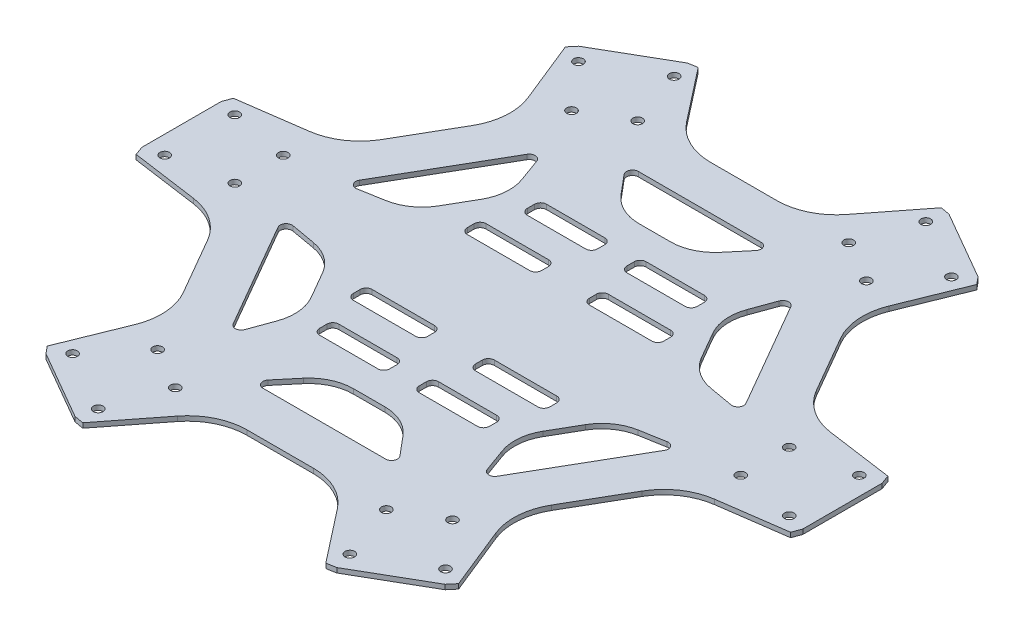
SolidWorks part; units mm, degrees
ref_plane "Front Plane" through (0, 0, 0) normal (0, 0, 1) x (1, 0, 0)
ref_plane "Top Plane" through (0, 0, 0) normal (0, 1, 0) x (1, 0, 0)
ref_plane "Right Plane" through (0, 0, 0) normal (1, 0, 0) x (0, 0, -1)
sketch "Sketch1" plane through (0, 0, 0) normal (0, 1, 0) x (1, 0, 0)
  line L0 (0, 0) -> (-41.6039, 24.02)
  line L1 (-67.498, 38.97) -> (-73.0745, 29.3112)
  line L2 (-87.6116, 19.5059) -> (-110.0668, 16.35)
  line L3 (-110.0668, 16.35) -> (-111.1613, 13.343)
  line L4 (-111.1613, 13.343) -> (-111.1613, 0)
  line L5 (-111.1613, 0) -> (0, 0) construction
  line L6 (-111.1613, 0) -> (-111.1613, -13.343)
  line L7 (-67.498, 38.97) -> (-54.6808, 31.57)
  line L8 (-54.6808, 31.57) -> (-64.9933, 13.7082)
  line L9 (-62.914, 10.7386) -> (-54.614, 12.2021)
  line L10 (-41.6039, 24.02) -> (-44.2284, 19.4742)
  line L11 (-74.306, 16.7755) -> (-53.7192, 4.8897) construction
  line L12 (-65.2613, 17.913) -> (-65.2613, 6.5078) construction
  line L13 (-110.0668, 16.35) -> (-98.8081, 16.35) construction
  line L14 (-62.914, 10.7386) -> (-55.1218, 10.7386) construction
  line L15 (-111.1613, -13.343) -> (-110.0668, -16.35)
  line L16 (-110.0668, -16.35) -> (-87.6116, -19.5059)
  line L17 (-73.0745, -29.3112) -> (-67.498, -38.97)
  line L18 (-67.498, -38.97) -> (-54.6808, -31.57)
  line L19 (-54.6808, -31.57) -> (-64.9933, -13.7082)
  line L20 (-62.914, -10.7386) -> (-54.614, -12.2021)
  line L21 (-44.2284, -19.4742) -> (-41.6039, -24.02)
  line L22 (-41.6039, -24.02) -> (0, 0)
  line L23 (-110.0668, 16.35) -> (-110.0668, -16.35) construction
  line L24 (-87.6116, 19.5059) -> (-87.6116, -19.5059) construction
  line L25 (-105.0363, 11.7806) -> (-105.0363, -11.7806) construction
  line L26 (-85.0763, 8.1431) -> (-85.0763, -8.1431) construction
  line L27 (-108.5636, 12.9259) -> (-103.4648, 13.6425) construction
  line L28 (-106.6613, 12.7082) -> (-106.6613, 10.217) construction
  line L29 (-88.9827, 9.2351) -> (-84.0445, 9.9291) construction
  line L30 (-86.7013, 8.8509) -> (-86.7013, 6.1232) construction
  arc A0 (-73.0745, 29.3112) -> (-87.6116, 19.5059) centre (-90.395, 39.3112) cw
  arc A1 (-64.9933, 13.7082) -> (-62.914, 10.7386) centre (-63.2613, 12.7082) ccw
  arc A2 (-54.614, 12.2021) -> (-44.2284, 19.4742) centre (-57.2187, 26.9742) ccw
  arc A3 (-87.6116, -19.5059) -> (-73.0745, -29.3112) centre (-90.395, -39.3112) cw
  arc A4 (-64.9933, -13.7082) -> (-62.914, -10.7386) centre (-63.2613, -12.7082) cw
  arc A5 (-54.614, -12.2021) -> (-44.2284, -19.4742) centre (-57.2187, -26.9742) cw
  circle A6 centre (-105.0363, 11.7806) radius 1.625
  circle A7 centre (-85.0763, 8.1431) radius 1.625
  circle A8 centre (-105.0363, -11.7806) radius 1.625
  circle A9 centre (-85.0763, -8.1431) radius 1.625
  point P45 (-85.0763, 0)
  point P46 (-105.0363, 0)
  dimension "D5" = 20
  dimension "D7" = 22.625
  dimension "D8" = 2
  dimension "D9" = 15
  dimension "D17" = 3.25
  dimension "D2" = 30
  dimension "D3" = 3.2
  dimension "D4" = 20
  dimension "D6" = 8
  dimension "D10" = 14.8
  dimension "D11" = 15.1
  dimension "D12" = 48.04
  dimension "D13" = 45.9
  dimension "D14" = 10
  dimension "D15" = 16.35
  dimension "D16" = 30
  dimension "D18" = 4.5
  dimension "D19" = 3.6
  dimension "D20" = 24.46
  dimension "D21" = 9.98
extrude "Boss-Extrude1" add sketch "Sketch1" along normal blind 1.6
pattern_circular "CirPattern2" count 6 every 60 about axis through (0, 1.6, 0) along (0, -1, 0) of "Boss-Extrude1"
sketch "Sketch2" plane through (0, 0, 0) normal (0, 1, 0) x (1, 0, 0)
  line L0 (-26.56, 38.16) -> (-6.96, 38.16)
  line L1 (-4.96, 36.16) -> (-4.96, 33.7)
  line L2 (-6.96, 31.7) -> (-26.56, 31.7)
  line L3 (-28.56, 33.7) -> (-28.56, 36.16)
  line L4 (-31.05, 22.33) -> (-10.05, 22.33)
  line L5 (-8.05, 20.33) -> (-8.05, 18)
  line L6 (-10.05, 16) -> (-31.05, 16)
  line L7 (-33.05, 18) -> (-33.05, 20.33)
  arc A0 (-6.96, 38.16) -> (-4.96, 36.16) centre (-6.96, 36.16) cw
  arc A1 (-4.96, 33.7) -> (-6.96, 31.7) centre (-6.96, 33.7) cw
  arc A2 (-26.56, 31.7) -> (-28.56, 33.7) centre (-26.56, 33.7) cw
  arc A3 (-28.56, 36.16) -> (-26.56, 38.16) centre (-26.56, 36.16) cw
  arc A4 (-10.05, 22.33) -> (-8.05, 20.33) centre (-10.05, 20.33) cw
  arc A5 (-8.05, 18) -> (-10.05, 16) centre (-10.05, 18) cw
  arc A6 (-31.05, 16) -> (-33.05, 18) centre (-31.05, 18) cw
  arc A7 (-33.05, 20.33) -> (-31.05, 22.33) centre (-31.05, 20.33) cw
  dimension "D3" = 2
  dimension "D8" = 2
  dimension "D1" = 23.6
  dimension "D2" = 6.46
  dimension "D4" = 4.96
  dimension "D5" = 31.7
  dimension "D6" = 25
  dimension "D7" = 6.33
  dimension "D9" = 8.05
  dimension "D10" = 16
extrude "Cut-Extrude1" cut sketch "Sketch2" along normal through all
mirror "Mirror5" about plane through (0, 0, 0) normal (0, 0, 1) of "Cut-Extrude1"
mirror "Mirror6" about plane through (0, 0, 0) normal (1, 0, 0) of "Mirror5"
sketch "Sketch4" plane through (0, 1.6, 0) normal (0, 1, 0) x (1, 0, 0)
  line L0 (-35.486, -77.7498) -> (35.486, 77.7498) construction
  line L1 (1.6555, 0) -> (0, 0) construction
  circle A0 centre (-35.486, -77.7498) radius 1.625
  circle A1 centre (-35.486, -77.7498) radius 1.625 construction
  circle A2 centre (35.486, 77.7498) radius 1.625
  circle A3 centre (35.486, 77.7498) radius 1.625 construction
  dimension "D1" = 170.9302
  dimension "D2" = 65.467
